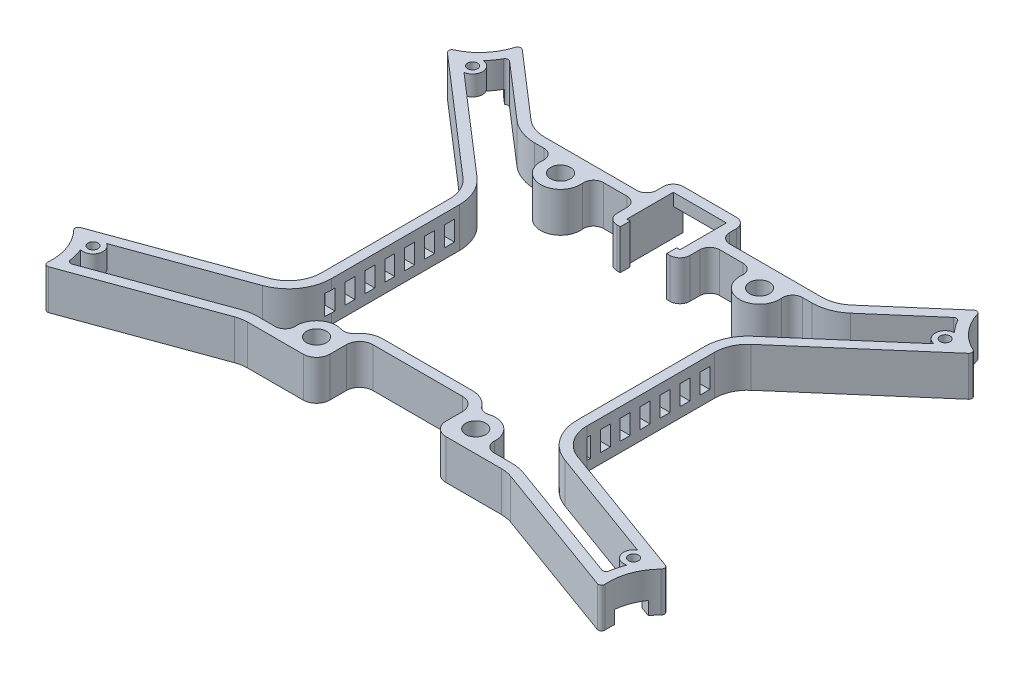
SolidWorks part; units mm, degrees
material "Sculpteo SLS"
ref_plane "Front Plane" through (0, 0, 0) normal (0, 0, 1) x (1, 0, 0)
ref_plane "Top Plane" through (0, 0, 0) normal (0, 1, 0) x (1, 0, 0)
ref_plane "Right Plane" through (0, 0, 0) normal (1, 0, 0) x (0, 0, -1)
sketch "Sketch1" plane through (0, 0, 0) normal (0, 1, 0) x (1, 0, 0)
  line L0 (8, 53) -> (8, 55)
  line L5 (8, 55) -> (-8, 55)
  line L6 (-8, 55) -> (-8, 53)
  line L7 (-14, 47) -> (-41.7933, 47)
  line L8 (-50.3032, 50.1724) -> (-67.8698, 65.3837)
  line L9 (-74.4159, 57.824) -> (-41.4901, 29.313)
  line L10 (-37, 19.4854) -> (-37, -19.0433)
  line L11 (-45.5537, -31.2593) -> (-84.4853, -45.4292)
  line L12 (-81.065, -54.8262) -> (-42.683, -40.8562)
  line L13 (-38.2367, -40.0722) -> (-21.5, -40.0722)
  line L14 (-20.5, -39.0722) -> (-20.5, -34.0722)
  line L15 (-13.5, -27.0722) -> (13.5, -27.0722)
  line L16 (20.5, -34.0722) -> (20.5, -39.0722)
  line L17 (21.5, -40.0722) -> (38.2367, -40.0722)
  line L18 (42.683, -40.8562) -> (81.065, -54.8262)
  line L19 (84.4853, -45.4292) -> (45.5537, -31.2593)
  line L20 (37, -19.0433) -> (37, 19.4854)
  line L21 (41.4901, 29.313) -> (74.4159, 57.824)
  line L22 (67.8698, 65.3837) -> (50.3032, 50.1724)
  line L23 (41.7933, 47) -> (14, 47)
  line L27 (11, 53) -> (11, 55)
  line L28 (8, 58) -> (-8, 58)
  line L31 (-11, 55) -> (-11, 53)
  line L32 (-14, 50) -> (-41.7933, 50)
  line L33 (-48.3393, 52.4403) -> (-69.5576, 70.8135)
  line L34 (-80.0313, 58.718) -> (-43.4539, 27.0451)
  line L35 (-40, 19.4854) -> (-40, -19.0433)
  line L36 (-46.5798, -28.4402) -> (-90.0503, -44.2622)
  line L37 (-84.578, -59.2973) -> (-41.6569, -43.6753)
  line L38 (-38.2367, -43.0722) -> (-21.5, -43.0722)
  line L39 (-17.5, -39.0722) -> (-17.5, -34.0722)
  line L40 (-13.5, -30.0722) -> (13.5, -30.0722)
  line L41 (17.5, -34.0722) -> (17.5, -39.0722)
  line L43 (21.5, -43.0722) -> (38.2367, -43.0722)
  line L64 (41.6569, -43.6753) -> (84.578, -59.2973)
  line L65 (90.0503, -44.2622) -> (46.5798, -28.4402)
  line L66 (40, -19.0433) -> (40, 19.4854)
  line L67 (43.4539, 27.0451) -> (80.0313, 58.718)
  line L68 (69.5576, 70.8135) -> (48.3393, 52.4403)
  line L69 (41.7933, 50) -> (14, 50)
  line L70 (11, 53) -> (11, 55)
  line L71 (8, 58) -> (-8, 58)
  line L72 (-11, 55) -> (-11, 53)
  line L73 (-14, 50) -> (-41.7933, 50)
  line L74 (-48.3393, 52.4403) -> (-69.2881, 70.5802)
  line L75 (-79.7618, 58.4847) -> (-43.4539, 27.0451)
  line L76 (-40, 19.4854) -> (-40, -19.0433)
  line L77 (-46.5798, -28.4402) -> (-89.7154, -44.1403)
  line L78 (-84.2431, -59.1754) -> (-41.6569, -43.6753)
  line L79 (-38.2367, -43.0722) -> (-21.5, -43.0722)
  line L80 (-17.5, -39.0722) -> (-17.5, -34.0722)
  line L81 (-13.5, -30.0722) -> (13.5, -30.0722)
  line L82 (17.5, -34.0722) -> (17.5, -39.0722)
  line L83 (21.5, -43.0722) -> (38.2367, -43.0722)
  line L104 (41.6569, -43.6753) -> (84.2431, -59.1754)
  line L105 (89.7154, -44.1403) -> (46.5798, -28.4402)
  line L106 (40, -19.0433) -> (40, 19.4854)
  line L107 (43.4539, 27.0451) -> (79.7618, 58.4847)
  line L108 (69.2881, 70.5802) -> (48.3393, 52.4403)
  line L109 (41.7933, 50) -> (14, 50)
  line L111 (-48.3393, 52.4403) -> (-69.5576, 70.8135) construction
  line L112 (-50.3032, 50.1724) -> (-71.5214, 68.5456) construction
  line L113 (-78.0674, 60.9859) -> (-41.4901, 29.313) construction
  line L114 (-80.0313, 58.718) -> (-43.4539, 27.0451) construction
  line L115 (43.4539, 27.0451) -> (80.0313, 58.718) construction
  line L116 (41.4901, 29.313) -> (78.0674, 60.9859) construction
  line L117 (71.5214, 68.5456) -> (50.3032, 50.1724) construction
  line L118 (69.5576, 70.8135) -> (48.3393, 52.4403) construction
  line L119 (41.6569, -43.6753) -> (84.578, -59.2973) construction
  line L120 (42.683, -40.8562) -> (85.604, -56.4782) construction
  line L121 (89.0243, -47.0813) -> (45.5537, -31.2593) construction
  line L122 (90.0503, -44.2622) -> (46.5798, -28.4402) construction
  line L123 (-46.5798, -28.4402) -> (-90.0503, -44.2622) construction
  line L124 (-45.5537, -31.2593) -> (-89.0243, -47.0813) construction
  line L125 (-85.604, -56.4782) -> (-42.683, -40.8562) construction
  line L126 (-84.578, -59.2973) -> (-41.6569, -43.6753) construction
  arc A0 (8, 55) -> (8, 55) centre (8, 55) ccw
  arc A1 (-8, 55) -> (-8, 55) centre (-8, 55) ccw
  arc A2 (-14, 47) -> (-8, 53) centre (-14, 53) ccw
  arc A3 (-50.3032, 50.1724) -> (-41.7933, 47) centre (-41.7933, 60) ccw
  arc A9 (-37, 19.4854) -> (-41.4901, 29.313) centre (-50, 19.4854) ccw
  arc A10 (-45.5537, -31.2593) -> (-37, -19.0433) centre (-50, -19.0433) ccw
  arc A14 (-38.2367, -40.0722) -> (-42.683, -40.8562) centre (-38.2367, -53.0722) ccw
  arc A15 (-21.5, -40.0722) -> (-20.5, -39.0722) centre (-21.5, -39.0722) ccw
  arc A16 (-13.5, -27.0722) -> (-20.5, -34.0722) centre (-13.5, -34.0722) ccw
  arc A17 (20.5, -34.0722) -> (13.5, -27.0722) centre (13.5, -34.0722) ccw
  arc A18 (20.5, -39.0722) -> (21.5, -40.0722) centre (21.5, -39.0722) ccw
  arc A19 (42.683, -40.8562) -> (38.2367, -40.0722) centre (38.2367, -53.0722) ccw
  arc A23 (37, -19.0433) -> (45.5537, -31.2593) centre (50, -19.0433) ccw
  arc A24 (41.4901, 29.313) -> (37, 19.4854) centre (50, 19.4854) ccw
  arc A28 (41.7933, 47) -> (50.3032, 50.1724) centre (41.7933, 60) ccw
  arc A29 (8, 53) -> (14, 47) centre (14, 53) ccw
  arc A30 (11, 55) -> (8, 58) centre (8, 55) ccw
  arc A31 (-8, 58) -> (-11, 55) centre (-8, 55) ccw
  arc A32 (-14, 50) -> (-11, 53) centre (-14, 53) ccw
  arc A33 (-48.3393, 52.4403) -> (-41.7933, 50) centre (-41.7933, 60) ccw
  arc A34 (-72.7842, 76.2531) -> (-69.5576, 70.8135) centre (-63.0115, 78.3732) ccw
  arc A35 (-72.7842, 76.2531) -> (-85.8763, 61.1337) centre (-85, 73.603) ccw
  arc A36 (-80.0313, 58.718) -> (-85.8763, 61.1337) centre (-86.5773, 51.1583) ccw
  arc A37 (-40, 19.4854) -> (-43.4539, 27.0451) centre (-50, 19.4854) ccw
  arc A38 (-46.5798, -28.4402) -> (-40, -19.0433) centre (-50, -19.0433) ccw
  arc A39 (-96.3725, -44.4349) -> (-90.0503, -44.2622) centre (-93.4705, -34.8653) ccw
  arc A40 (-96.3725, -44.4349) -> (-89.5321, -63.2288) centre (-100, -56.397) ccw
  arc A41 (-84.578, -59.2973) -> (-89.5321, -63.2288) centre (-81.1578, -68.6942) ccw
  arc A42 (-38.2367, -43.0722) -> (-41.6569, -43.6753) centre (-38.2367, -53.0722) ccw
  arc A43 (-21.5, -43.0722) -> (-17.5, -39.0722) centre (-21.5, -39.0722) ccw
  arc A44 (-13.5, -30.0722) -> (-17.5, -34.0722) centre (-13.5, -34.0722) ccw
  arc A45 (17.5, -34.0722) -> (13.5, -30.0722) centre (13.5, -34.0722) ccw
  arc A46 (17.5, -39.0722) -> (21.5, -43.0722) centre (21.5, -39.0722) ccw
  arc A47 (41.6569, -43.6753) -> (38.2367, -43.0722) centre (38.2367, -53.0722) ccw
  arc A48 (89.5321, -63.2288) -> (84.578, -59.2973) centre (81.1578, -68.6942) ccw
  arc A49 (89.5321, -63.2288) -> (96.3725, -44.4349) centre (100, -56.397) ccw
  arc A50 (90.0503, -44.2622) -> (96.3725, -44.4349) centre (93.4705, -34.8653) ccw
  arc A51 (40, -19.0433) -> (46.5798, -28.4402) centre (50, -19.0433) ccw
  arc A52 (43.4539, 27.0451) -> (40, 19.4854) centre (50, 19.4854) ccw
  arc A53 (85.8763, 61.1337) -> (80.0313, 58.718) centre (86.5773, 51.1583) ccw
  arc A54 (85.8763, 61.1337) -> (72.7842, 76.2531) centre (85, 73.603) ccw
  arc A55 (69.5576, 70.8135) -> (72.7842, 76.2531) centre (63.0115, 78.3732) ccw
  arc A84 (41.7933, 50) -> (48.3393, 52.4403) centre (41.7933, 60) ccw
  arc A85 (11, 53) -> (14, 50) centre (14, 53) ccw
  arc A86 (11, 55) -> (8, 58) centre (8, 55) ccw
  arc A87 (-8, 58) -> (-11, 55) centre (-8, 55) ccw
  arc A88 (-14, 50) -> (-11, 53) centre (-14, 53) ccw
  arc A89 (-48.3393, 52.4403) -> (-41.7933, 50) centre (-41.7933, 60) ccw
  arc A93 (-40, 19.4854) -> (-43.4539, 27.0451) centre (-50, 19.4854) ccw
  arc A94 (-46.5798, -28.4402) -> (-40, -19.0433) centre (-50, -19.0433) ccw
  arc A98 (-38.2367, -43.0722) -> (-41.6569, -43.6753) centre (-38.2367, -53.0722) ccw
  arc A99 (-21.5, -43.0722) -> (-17.5, -39.0722) centre (-21.5, -39.0722) ccw
  arc A100 (-13.5, -30.0722) -> (-17.5, -34.0722) centre (-13.5, -34.0722) ccw
  arc A101 (17.5, -34.0722) -> (13.5, -30.0722) centre (13.5, -34.0722) ccw
  arc A102 (17.5, -39.0722) -> (21.5, -43.0722) centre (21.5, -39.0722) ccw
  arc A103 (41.6569, -43.6753) -> (38.2367, -43.0722) centre (38.2367, -53.0722) ccw
  arc A107 (40, -19.0433) -> (46.5798, -28.4402) centre (50, -19.0433) ccw
  arc A108 (43.4539, 27.0451) -> (40, 19.4854) centre (50, 19.4854) ccw
  arc A140 (41.7933, 50) -> (48.3393, 52.4403) centre (41.7933, 60) ccw
  arc A141 (11, 53) -> (14, 50) centre (14, 53) ccw
  arc A142 (-79.7618, 58.4847) -> (-69.2881, 70.5802) centre (-85, 73.603) ccw
  arc A143 (-74.4159, 57.824) -> (-67.8698, 65.3837) centre (-85, 73.603) ccw
  arc A144 (67.8698, 65.3837) -> (74.4159, 57.824) centre (85, 73.603) ccw
  arc A145 (69.2881, 70.5802) -> (79.7618, 58.4847) centre (85, 73.603) ccw
  arc A146 (-81.065, -54.8262) -> (-84.4853, -45.4292) centre (-100, -56.397) ccw
  arc A147 (-84.2431, -59.1754) -> (-89.7154, -44.1403) centre (-100, -56.397) ccw
  arc A148 (84.4853, -45.4292) -> (81.065, -54.8262) centre (100, -56.397) ccw
  arc A149 (89.7154, -44.1403) -> (84.2431, -59.1754) centre (100, -56.397) ccw
  circle A151 centre (-85, 73.603) radius 19 construction
  circle A152 centre (-85, 73.603) radius 16 construction
  arc A196 (-72.7842, 76.2531) -> (-85.8763, 61.1337) centre (-85, 73.603) ccw construction
  arc A197 (-75.716, 75.6171) -> (-85.666, 64.1263) centre (-85, 73.603) ccw construction
  arc A198 (-72.7842, 76.2531) -> (-69.5576, 70.8135) centre (-63.0115, 78.3732) ccw construction
  arc A199 (-75.716, 75.6171) -> (-71.5214, 68.5456) centre (-63.0115, 78.3732) ccw construction
  arc A200 (-78.0674, 60.9859) -> (-85.666, 64.1263) centre (-86.5773, 51.1583) ccw construction
  arc A201 (-80.0313, 58.718) -> (-85.8763, 61.1337) centre (-86.5773, 51.1583) ccw construction
  arc A202 (85.8763, 61.1337) -> (72.7842, 76.2531) centre (85, 73.603) ccw construction
  arc A203 (85.666, 64.1263) -> (75.716, 75.6171) centre (85, 73.603) ccw construction
  arc A204 (71.5214, 68.5456) -> (75.716, 75.6171) centre (63.0115, 78.3732) ccw construction
  arc A205 (69.5576, 70.8135) -> (72.7842, 76.2531) centre (63.0115, 78.3732) ccw construction
  arc A206 (85.666, 64.1263) -> (78.0674, 60.9859) centre (86.5773, 51.1583) ccw construction
  arc A207 (85.8763, 61.1337) -> (80.0313, 58.718) centre (86.5773, 51.1583) ccw construction
  arc A208 (89.5321, -63.2288) -> (96.3725, -44.4349) centre (100, -56.397) ccw construction
  arc A209 (92.0444, -61.5892) -> (97.2431, -47.3058) centre (100, -56.397) ccw construction
  arc A210 (89.0243, -47.0813) -> (97.2431, -47.3058) centre (93.4705, -34.8653) ccw construction
  arc A211 (90.0503, -44.2622) -> (96.3725, -44.4349) centre (93.4705, -34.8653) ccw construction
  arc A212 (92.0444, -61.5892) -> (85.604, -56.4782) centre (81.1578, -68.6942) ccw construction
  arc A213 (89.5321, -63.2288) -> (84.578, -59.2973) centre (81.1578, -68.6942) ccw construction
  arc A214 (-96.3725, -44.4349) -> (-89.5321, -63.2288) centre (-100, -56.397) ccw construction
  arc A215 (-97.2431, -47.3058) -> (-92.0444, -61.5892) centre (-100, -56.397) ccw construction
  arc A216 (-84.578, -59.2973) -> (-89.5321, -63.2288) centre (-81.1578, -68.6942) ccw construction
  arc A217 (-85.604, -56.4782) -> (-92.0444, -61.5892) centre (-81.1578, -68.6942) ccw construction
  arc A218 (-97.2431, -47.3058) -> (-89.0243, -47.0813) centre (-93.4705, -34.8653) ccw construction
  arc A219 (-96.3725, -44.4349) -> (-90.0503, -44.2622) centre (-93.4705, -34.8653) ccw construction
  point P31 (-43.7365, 50.8076)
  point P34 (-61.9185, 68.9896)
  point P52 (-68.9896, 61.9185)
  point P55 (-40.8076, 33.7365)
  point P68 (-44.506, -35.2366)
  point P69 (-79.8779, -51.7308)
  point P108 (-75.6518, -60.7939)
  point P109 (-43.2771, -45.6973)
  point P126 (43.2771, -45.6973)
  point P127 (75.6518, -60.7939)
  point P133 (79.8779, -51.7308)
  point P134 (44.506, -35.2366)
  point P139 (40.8076, 33.7365)
  point P140 (68.9896, 61.9185)
  point P146 (61.9185, 68.9896)
  point P147 (43.7365, 50.8076)
  point P161 (-75, 75)
  point P163 (-58.5124, 80.0408)
  point P172 (-59.6991, 79.6779)
  point P179 (-56, 75)
  dimension "D3" = 32
  dimension "D1" = 0
  dimension "D2" = 3
  dimension "D4" = 3
extrude "Boss-Extrude1" add sketch "Sketch1" along normal blind 12
fillet "Fillet1" radius 1 16 edges at (-69.2881, 6, -70.5802) (-67.8698, 6, -65.3837) (-74.4159, 6, -57.824) (-79.7618, 6, -58.4847) (74.4159, 6, -57.824) (79.7618, 6, -58.4847) (69.2881, 6, -70.5802) (67.8698, 6, -65.3837) (89.7154, 6, 44.1403) (84.4853, 6, 45.4292) (81.065, 6, 54.8262) (84.2431, 6, 59.1754) (-89.7154, 6, 44.1403) (-84.4853, 6, 45.4292) (-81.065, 6, 54.8262) (-84.2431, 6, 59.1754)
sketch "Sketch2" plane through (0, 0, 0) normal (0, -1, 0) x (1, 0, 0)
  line L0 (0, 0) -> (-37723.2212, -32665.1925) construction
  line L1 (0, 0) -> (37723.2212, -32665.1925) construction
  line L2 (-1.4293, 20.5202) -> (-46778.3227, 17045.9171) construction
  line L3 (1.4463, 20.5264) -> (46769.1018, 17042.5609) construction
  line L4 (-79.8758, 54.3933) -> (-42.683, 40.8562) construction
  line L5 (42.683, 40.8562) -> (79.8758, 54.3933) construction
  line L6 (-73.4591, -56.9955) -> (-41.4901, -29.313) construction
  line L7 (41.4901, -29.313) -> (73.4591, -56.9955) construction
  line L8 (-87.9027, 56.2507) -> (-69.1089, 49.4103)
  line L9 (-69.1089, 49.4103) -> (-71.845, 41.8927)
  line L10 (-71.845, 41.8927) -> (-90.6389, 48.7331)
  line L11 (-90.6389, 48.7331) -> (-87.9027, 56.2507)
  line L12 (0, 0) -> (0, -50000) construction
  line L13 (-63.096, -49.3447) -> (-78.2154, -62.4368)
  line L14 (-78.2154, -62.4368) -> (-72.9785, -68.4846)
  line L15 (-72.9785, -68.4846) -> (-57.8591, -55.3924)
  line L16 (-57.8591, -55.3924) -> (-63.096, -49.3447)
  line L17 (57.8591, -55.3924) -> (63.096, -49.3447)
  line L18 (72.9785, -68.4846) -> (57.8591, -55.3924)
  line L19 (78.2154, -62.4368) -> (72.9785, -68.4846)
  line L20 (63.096, -49.3447) -> (78.2154, -62.4368)
  line L21 (90.6389, 48.7331) -> (87.9027, 56.2507)
  line L22 (71.845, 41.8927) -> (90.6389, 48.7331)
  line L23 (69.1089, 49.4103) -> (71.845, 41.8927)
  line L24 (87.9027, 56.2507) -> (69.1089, 49.4103)
  point P22 (0, 20)
  dimension "D1" = 20
  dimension "D2" = 8
  dimension "D3" = 75
  dimension "D4" = 80
extrude "Cut-Extrude1" cut sketch "Sketch2" against normal blind 4
sketch "Sketch3" plane through (0, 12, 0) normal (0, 1, 0) x (1, 0, 0)
  line L0 (-14, 50) -> (-41.7933, 50) construction
  line L1 (0, 0) -> (0, -50000) construction
  line L2 (-38.2367, -43.0722) -> (-21.5, -43.0722) construction
  circle A0 centre (-30, 43) radius 3
  circle A1 centre (-30, 43) radius 6
  circle A2 centre (30, 43) radius 6
  circle A3 centre (30, 43) radius 3
  circle A4 centre (-24, -36.5722) radius 3
  circle A5 centre (-24, -36.5722) radius 6
  circle A6 centre (24, -36.5722) radius 6
  circle A7 centre (24, -36.5722) radius 3
  dimension "D2" = 6
  dimension "D1" = 7
  dimension "D3" = 30
  dimension "D5" = 6.5
  dimension "D6" = 24
  dimension "D4" = 3
extrude "Boss-Extrude2" add sketch "Sketch3" against normal up to surface (12 mm away) up to face at (-63.2019, 0, -3.3996)
sketch "Sketch4" plane through (0, 2.0205, 0) normal (0, 0, -1) x (-1, 0, 0)
  line L0 (8, -2.0205) -> (11, -2.0205) construction
  line L1 (-8, 6.2795) -> (8, 6.2795)
  line L2 (-8, 6.2795) -> (-8, -2.0205)
  line L3 (-8, -2.0205) -> (8, -2.0205)
  line L4 (8, 6.2795) -> (8, -2.0205)
  point P6 (0, 6.2795)
  dimension "D1" = 16
  dimension "D2" = 8.3
extrude "Cut-Extrude2" cut sketch "Sketch4" along normal through all
sketch "Sketch5" plane through (0, 0, 0) normal (0, -1, 0) x (1, 0, 0)
  line L0 (-8, -55) -> (-8, -41)
  line L2 (-11, -38) -> (-11, -55)
  line L3 (-11, -55) -> (-8, -55)
  line L4 (0, 0) -> (0, -50000) construction
  line L9 (-11, -38) -> (-7, -38)
  line L10 (-7, -38) -> (-7, -41)
  line L11 (-7, -41) -> (-8, -41)
  line L12 (7, -41) -> (8, -41)
  line L13 (7, -38) -> (7, -41)
  line L14 (11, -38) -> (7, -38)
  line L15 (11, -55) -> (8, -55)
  line L16 (11, -38) -> (11, -55)
  line L17 (8, -55) -> (8, -41)
  line L18 (-8, -58) -> (-8, -53) construction
  dimension "D1" = 17
  dimension "D2" = 1
  dimension "D3" = 3
extrude "Boss-Extrude3" add sketch "Sketch5" against normal up to surface (12 mm away) up to face at (0, 12, -8.4115)
fillet "Fillet2" radius 3 12 edges at (-20.1714, 6, 31.9525) (-28.8734, 6, 40.0722) (20.1714, 6, 31.9525) (28.8734, 6, 40.0722) (25.5279, 6, -47) (34.4721, 6, -47) (-25.5279, 6, -47) (-34.4721, 6, -47) (-11, 6, -38) (11, 6, -38) (11, 6, -47.8038) (-11, 6, -47.8038)
sketch "Sketch6" plane through (40, 0, 0) normal (1, 0, 0) x (0, 0, -1)
  line L0 (-19.0433, 0) -> (19.4854, 0) construction
  line L1 (-21, 9) -> (-18, 9)
  line L2 (-21, 9) -> (-21, 3)
  line L3 (-21, 3) -> (-18, 3)
  line L4 (-18, 9) -> (-18, 3)
  line L5 (-15, 9) -> (-15, 3)
  line L6 (-15, 9) -> (-12, 9)
  line L7 (-12, 9) -> (-12, 3)
  line L8 (-15, 3) -> (-12, 3)
  line L9 (-9, 9) -> (-9, 3)
  line L10 (-9, 9) -> (-6, 9)
  line L11 (-6, 9) -> (-6, 3)
  line L12 (-9, 3) -> (-6, 3)
  line L13 (-3, 9) -> (-3, 3)
  line L14 (-3, 9) -> (0, 9)
  line L15 (0, 9) -> (0, 3)
  line L16 (-3, 3) -> (0, 3)
  line L17 (3, 9) -> (3, 3)
  line L18 (3, 9) -> (6, 9)
  line L19 (6, 9) -> (6, 3)
  line L20 (3, 3) -> (6, 3)
  line L21 (9, 9) -> (9, 3)
  line L22 (9, 9) -> (12, 9)
  line L23 (12, 9) -> (12, 3)
  line L24 (9, 3) -> (12, 3)
  line L25 (15, 9) -> (15, 3)
  line L26 (15, 9) -> (18, 9)
  line L27 (18, 9) -> (18, 3)
  line L28 (15, 3) -> (18, 3)
  dimension "D1" = 3
  dimension "D2" = 6
  dimension "D3" = 3
  dimension "D4" = 21
  dimension "D5" = 7
extrude "Cut-Extrude3" cut sketch "Sketch6" against normal through all
sketch "Sketch7" plane through (0, 12, 0) normal (0, 1, 0) x (1, 0, 0)
  line L0 (-46.5798, -28.4402) -> (-88.1785, -43.5809) construction
  line L1 (-78.5254, 57.4141) -> (-43.4539, 27.0451) construction
  line L2 (0, 0) -> (0, -50000) construction
  circle A0 centre (-81.4949, -46.4692) radius 3
  arc A1 (-84.0454, -57.6011) -> (-88.552, -45.2192) centre (-100, -56.397) ccw construction
  circle A2 centre (-71.2513, 57.7293) radius 3
  arc A3 (-78.2902, 59.0779) -> (-69.6648, 69.0389) centre (-85, 73.603) ccw construction
  circle A4 centre (71.2513, 57.7293) radius 3
  circle A5 centre (81.4949, -46.4692) radius 3
  dimension "D1" = 6
  dimension "D2" = 21
  dimension "D3" = 5
  dimension "D4" = 21
  dimension "D5" = 5
extrude "Boss-Extrude4" add sketch "Sketch7" against normal blind 6
sketch "Sketch8" plane through (0, 12, 0) normal (0, 1, 0) x (1, 0, 0)
  circle A0 centre (-71.2513, 57.7293) radius 1.5
  circle A1 centre (-81.4949, -46.4692) radius 1.5
  circle A2 centre (81.4949, -46.4692) radius 1.5
  circle A3 centre (71.2513, 57.7293) radius 1.5
  dimension "D1" = 3
extrude "Cut-Extrude4" cut sketch "Sketch8" against normal blind 3.2
